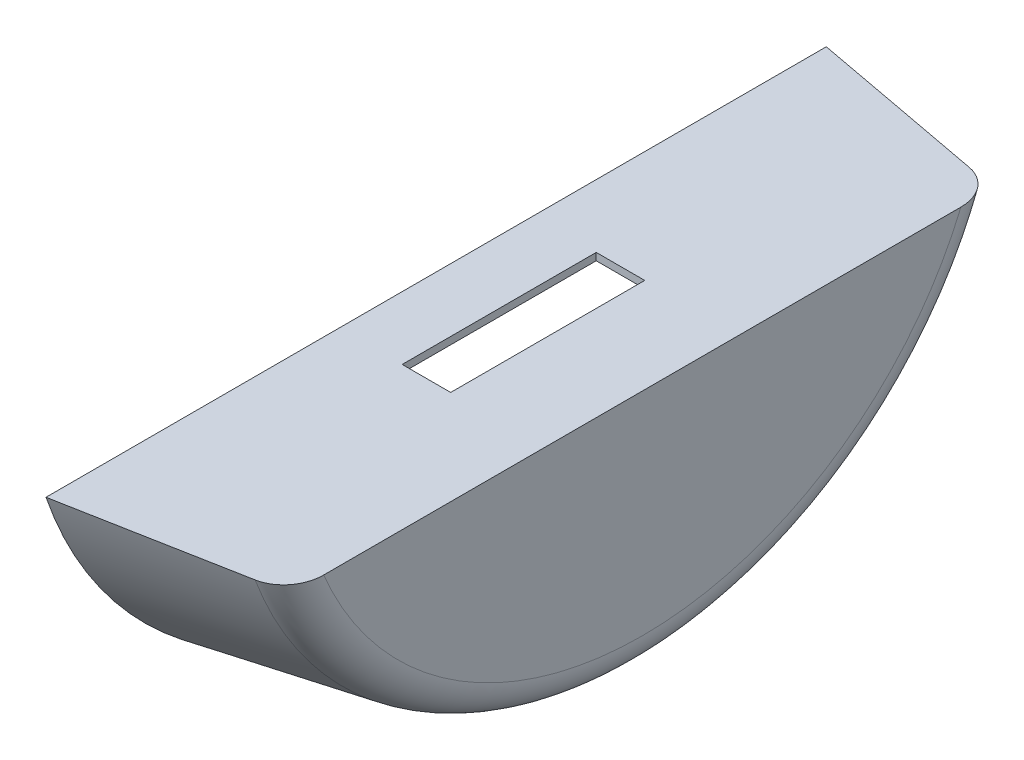
SolidWorks part; units mm, degrees
material "ABS"
ref_plane "Front Plane" through (0, 0, 0) normal (0, 0, 1) x (1, 0, 0)
ref_plane "Top Plane" through (0, 0, 0) normal (0, 1, 0) x (1, 0, 0)
ref_plane "Right Plane" through (0, 0, 0) normal (1, 0, 0) x (0, 0, -1)
sketch "Sketch1" plane through (0, 0, 0) normal (1, 0, 0) x (0, 0, -1)
  line L0 (-160.8571, -55) -> (160.8571, -55)
  arc A0 (-160.8571, -55) -> (160.8571, -55) centre (0, 0) ccw
  dimension "D1" = 340
  dimension "D2" = 55
extrude "Boss-Extrude1" add sketch "Sketch1" along normal blind 85
chamfer "Chamfer1" distance 85 distance2 15 1 edges at (85, -170, 0) first distance on face at (42.5, -112.5, 0)
fillet "Fillet2" radius 15 1 edges at (85, -155, 0)
shell "Shell1" thickness 3 removed face at (0, -112.5, 0)
sketch "Sketch2" plane through (0, -55, 0) normal (0, 1, 0) x (1, 0, 0)
  line L1 (26, 40) -> (46, 40)
  line L2 (26, 40) -> (26, -40)
  line L3 (26, -40) -> (46, -40)
  line L4 (46, 40) -> (46, -40)
  point P4 (26, 0)
  dimension "D1" = 80
  dimension "D2" = 20
  dimension "D3" = 26
extrude "Cut-Extrude1" cut sketch "Sketch2" against normal blind 10
